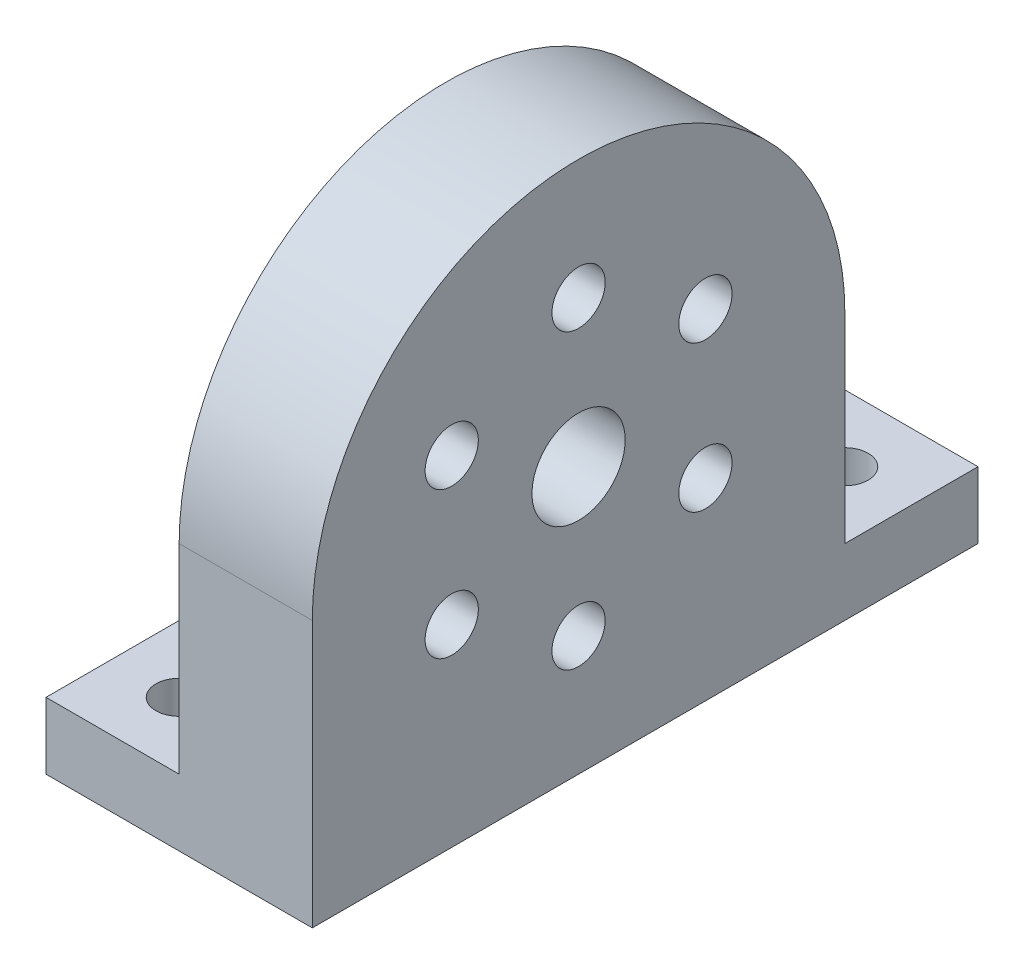
SolidWorks part; units mm, degrees
ref_plane "Front Plane" through (0, 0, 0) normal (0, 0, 1) x (1, 0, 0)
ref_plane "Top Plane" through (0, 0, 0) normal (0, 1, 0) x (1, 0, 0)
ref_plane "Right Plane" through (0, 0, 0) normal (1, 0, 0) x (0, 0, -1)
sketch "Sketch1" plane through (0, 0, 0) normal (1, 0, 0) x (0, 0, -1)
  line L0 (20, -15) -> (30, -15)
  line L1 (-30, -20) -> (30, -20)
  line L2 (-30, -20) -> (-30, -15)
  line L3 (-30, -15) -> (-20, -15)
  line L4 (30, -20) -> (30, -15)
  line L6 (-20, 0) -> (-20, -15)
  line L7 (-22.3599, -20) -> (-15.8566, -20)
  line L10 (20, 0) -> (20, -15)
  line L11 (17.6401, -20) -> (9.951, -20)
  line L12 (-20, -15) -> (-20, -20)
  circle A1 centre (0, 11) radius 2
  circle A2 centre (9.5263, 5.5) radius 2
  circle A3 centre (9.5263, -5.5) radius 2
  circle A4 centre (0, -11) radius 2
  circle A5 centre (-9.5263, -5.5) radius 2
  circle A6 centre (-9.5263, 5.5) radius 2
  arc A7 (20, 0) -> (-20, 0) centre (0, 0) ccw
  circle A8 centre (0, 0) radius 3.5
  point P18 (0, 0)
  dimension "D1" = 4
  dimension "D2" = 7
  dimension "D5" = 20
  dimension "D11" = 9.951
  dimension "D3" = 11
  dimension "D6" = 30
  dimension "D7" = 30
  dimension "D8" = 5
  dimension "D9" = 10
  dimension "D10" = 20
  dimension "D12" = 17.6401
  dimension "D13" = 15.8566
  dimension "D14" = 22.3599
  dimension "D4" = 6
extrude "Boss-Extrude1" add sketch "Sketch1" along normal blind 10 contours L10 A7 L6 L3 L2 L1 L4 L0 A8 A1 A2 A3 A4 A5 A6 region at (0, -15.6403, -25)
hole_wizard "CSK for M2 Flat Head Machine Screw1" positions "Sketch3" profile "Sketch4" countersink size "M2" standard "ANSI Metric" end condition through all
sketch "Sketch3" plane through (0, 0, 0) normal (-1, 0, 0) x (0, 0, 1)
  point P0 (0, 11)
  point P3 (9.5263, 5.5)
  point P6 (9.5263, -5.5)
  point P9 (0, -11)
  point P12 (-9.5263, -5.5)
  point P15 (-9.5263, 5.5)
sketch "Sketch4" plane through (0, 11, 0) normal (0, 1, 0) x (0, 0, 1)
  line L0 (0, 0) -> (0, 10)
  line L1 (0, 10) -> (1.5, 10)
  line L2 (1.5, 10) -> (1.5, 1.3)
  line L3 (1.5, 1.3) -> (2.8, 0)
  line L5 (2.8, 0) -> (0, 0)
  line L6 (-1.5, 1.3) -> (-2.8, 0) construction
  line L11 (0, -6.35) -> (0, 107.95) construction
  dimension "Thru Hole Dia." = 3
  dimension "Thru Hole Depth" = 10
  dimension "Near C'Sink Dia." = 5.6
  dimension "Near C'Sink Angle" = 90
sketch "Sketch6" plane through (0, -20, 0) normal (0, -1, 0) x (1, 0, 0)
  line L0 (0, 20) -> (-10, 20)
  line L1 (-10, 20) -> (-10, 10)
  line L2 (-10, 10) -> (0, 10)
  line L3 (0, 20) -> (0, -30) construction
  line L4 (0, 20) -> (10, 20)
  line L5 (10, 20) -> (10, 10)
  line L6 (10, 20) -> (10, -30) construction
  line L7 (10, 10) -> (0, 10)
  dimension "D1" = 10
  dimension "D2" = 10
extrude "Boss-Extrude2" add sketch "Sketch6" against normal blind 5
hole_wizard "Ø3.0mm Dowel Hole1" positions "3DSketch1" profile "Sketch7" hole size "Ø3.0" standard "ANSI Metric"
sketch3d "3DSketch1"
  line L5 (0, -15, 20) -> (-10, -15, 20) construction
  line L6 (-10, -15, 20) -> (-10, -15, 10) construction
  line L7 (10, -15, -20) -> (10, -15, -30) construction
  line L8 (10, -15, -30) -> (0, -15, -30) construction
  point P0 (5, -15, -25)
  point P2 (-5, -15, 15)
  point P5 (0, 0, 0)
  point P12 (0, 0, 0)
  point P17 (0, 0, 0)
  point P18 (0, 0, 0)
  dimension "D1" = 5
  dimension "D2" = 5
  dimension "D3" = 5
  dimension "D4" = 5
sketch "Sketch7" plane through (5, -15, -25) normal (1, 0, 0) x (0, 0, 1)
  line L0 (0, 0) -> (0, 5)
  line L1 (0, 5) -> (1.75, 5)
  line L2 (1.75, 5) -> (1.75, 0)
  line L5 (1.75, 0) -> (0, 0)
  line L10 (0, 5) -> (-1.75, 5) construction
  line L11 (0, -6.35) -> (0, 107.95) construction
  dimension "Hole Dia." = 3.5
  dimension "Hole Depth" = 5
  dimension "Drill Angle" = 180
